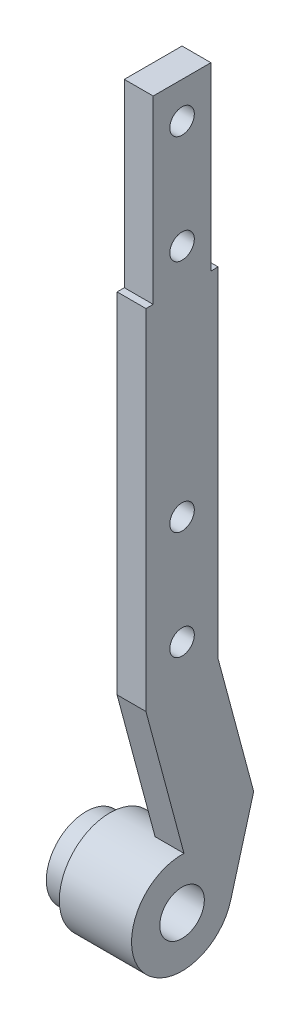
SolidWorks part; units mm, degrees
ref_plane "Front" through (0, 0, 0) normal (0, 0, 1) x (1, 0, 0)
ref_plane "Top" through (0, 0, 0) normal (0, 1, 0) x (1, 0, 0)
ref_plane "Right" through (0, 0, 0) normal (1, 0, 0) x (0, 0, -1)
sketch "Sketch1" plane through (-20.145, 0, 0) normal (-1, 0, 0) x (0, 0, 1)
  line L0 (-5, 27.967) -> (-9.926, 9.5831)
  line L1 (5, 26.6505) -> (5, 100)
  line L2 (5, 100) -> (-5, 100)
  line L3 (-5, 100) -> (-5, 27.967)
  line L4 (-0.2667, 6.9949) -> (5, 26.6505)
  line L5 (-9.926, 9.5831) -> (-6.7448, -1.8729)
  line L6 (5, 75) -> (-5, 75) construction
  line L7 (0, 0) -> (0, 100) construction
  line L8 (-5, 87.5) -> (5, 87.5) construction
  line L9 (0, 95) -> (0, 80) construction
  line L10 (-5, 75) -> (-4, 75)
  line L11 (-4, 75) -> (-4, 100)
  line L12 (5, 75) -> (4, 75)
  line L13 (4, 75) -> (4, 100)
  circle A0 centre (0, 80) radius 1.7
  circle A1 centre (0, 95) radius 1.7
  circle A6 centre (0, 0) radius 3.0845
  arc A7 (-3.0391, 0.5274) -> (2.6861, -1.5163) centre (0, 0) ccw
  arc A8 (-3.0391, 0.5274) -> (2.6861, -1.5163) centre (0, 0) ccw construction
  circle A9 centre (0, 0) radius 7
  point P20 (0, 87.5)
  dimension "D2" = 14
  dimension "D7" = 3.4
  dimension "D8" = 3.4
  dimension "D3" = 10
  dimension "D4" = 10
  dimension "D5" = 10
  dimension "D6" = 100
  dimension "D9" = 15
  dimension "D10" = 25
  dimension "D11" = 1
  dimension "D1" = 0.1
extrude "Boss-Extrude1" add sketch "Sketch1" along normal blind 10 contours A9 A6 region at (-20.145, 4.0124, -5.4925)
extrude "Boss-Extrude2" add sketch "Sketch1<3>" against normal blind 3 from surface contours A9 starting at face at (-30.145, 0, 3.0845)
sketch "Sketch1<3>" plane through (-20.145, 0, 0) normal (-1, 0, 0) x (0, 0, 1) same geometry as "Sketch1"
extrude "Boss-Extrude3" add sketch "Sketch1<5>" along normal blind 4 contours A9 L4 L1 L2 L3 L0 L5 region at (-20.145, 49.6264, -0.767)
sketch "Sketch1<5>" plane through (-20.145, 0, 0) normal (-1, 0, 0) x (0, 0, 1) same geometry as "Sketch1"
sketch "Sketch2" plane through (-30.145, 0, 0) normal (-1, 0, 0) x (0, 0, 1)
  circle A1 centre (0, 0) radius 5.5
  circle A2 centre (0, 0) radius 3.5
  circle A3 centre (0, 0) radius 3.5
  dimension "D1" = 2
  dimension "D2" = 2
extrude "Boss-Extrude4" add sketch "Sketch2" along normal up to surface (3.305 mm away)
sketch "Sketch3" plane through (-20.145, 0, 0) normal (1, 0, 0) x (0, 0, -1)
  line L0 (5, 36) -> (-5, 36)
  line L1 (5, 75) -> (5, 27.967) construction
  line L2 (-5, 26.6505) -> (-5, 75) construction
  line L3 (5, 44) -> (-5, 44)
  line L4 (0, 44) -> (0, 36) construction
  line L5 (0, 47.5) -> (0, 32.5) construction
  circle A0 centre (0, 32.5) radius 1.7
  circle A1 centre (0, 47.5) radius 1.7
  point P10 (0, 0)
  point P11 (0, 40)
  point P16 (0, 40)
  dimension "D3" = 3.4
  dimension "D4" = 3.4
  dimension "D1" = 40
  dimension "D2" = 8
  dimension "D5" = 15
extrude "Cut-Extrude1" cut sketch "Sketch3" against normal up to surface (4 mm away) contours A1 | A0 up to face at (-24.145, 51.8992, -1.7349)
equation "\"D4@Sketch3\"=\"D3@Sketch3\""
